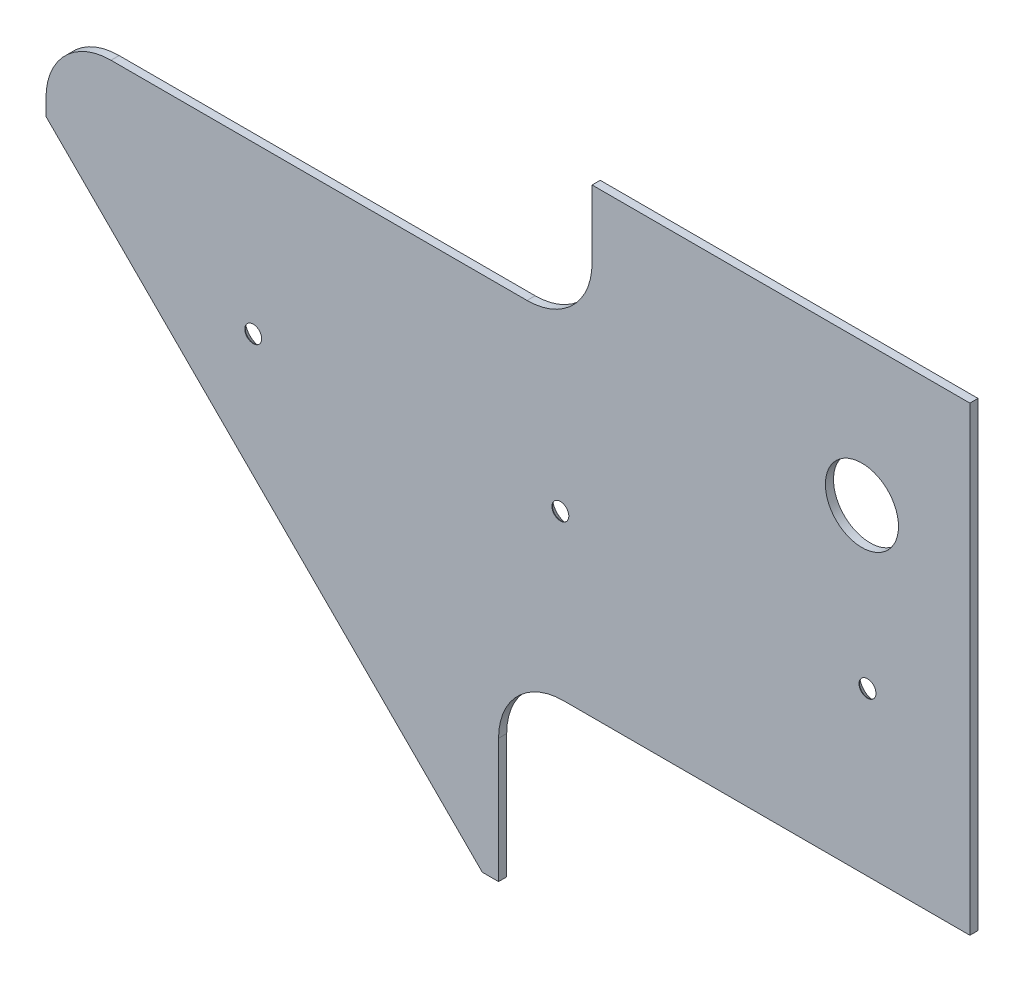
SolidWorks part; units mm, degrees
ref_plane "Front Plane" through (0, 0, 0) normal (0, 0, 1) x (1, 0, 0)
ref_plane "Top Plane" through (0, 0, 0) normal (0, 1, 0) x (1, 0, 0)
ref_plane "Right Plane" through (0, 0, 0) normal (1, 0, 0) x (0, 0, -1)
sketch "Sketch1" plane through (0, 0, 0) normal (0, 0, 1) x (1, 0, 0)
  line L0 (-138.2594, 48.9915) -> (32.2106, -121.4785)
  line L1 (32.2106, -121.4785) -> (222.7106, -121.4785)
  line L2 (-138.2594, 145.2215) -> (-138.2594, 48.9915)
  line L3 (-138.2594, 145.2215) -> (222.7106, 145.2215)
  line L4 (222.7106, -121.4785) -> (222.7106, 145.2215)
  circle A0 centre (180.538, 76.832) radius 14.2875
  circle A2 centre (180.538, 76.832) radius 64.9605 construction
  circle A3 centre (180.538, 76.832) radius 318.7974 construction
  point P0 (0, 0)
  point P2 (180.538, 76.832)
  dimension "D4" = 198.3105
  dimension "D1" = 45
  dimension "D2" = 266.7
  dimension "D5" = 245.11
extrude "Boss-Extrude1" add sketch "Sketch1" along normal blind 3.175
sketch "Sketch2" plane through (0, 0, 3.175) normal (0, 0, 1) x (1, 0, 0)
  line L0 (32.2106, -121.4785) -> (222.7106, -121.4785) construction
  line L1 (222.7634, -121.4785) -> (38.5606, -121.4785)
  line L2 (222.7634, -121.4785) -> (222.7634, -47.5645)
  line L3 (222.7634, -47.5645) -> (38.5606, -47.5645)
  line L4 (38.5606, -121.4785) -> (38.5606, -47.5645)
extrude "Cut-Extrude1" cut sketch "Sketch2" against normal through all contours L3 L4 L1 L2
fillet "Fillet1" radius 25.4 1 edges at (38.5606, -47.5645, 1.5875)
sketch "Sketch4" plane through (0, 0, 3.175) normal (0, 0, 1) x (1, 0, 0)
  line L1 (-138.2594, 145.2215) -> (-138.2594, 48.9915) construction
  line L3 (-138.2594, 145.2215) -> (75.1006, 145.2215)
  line L4 (-138.2594, 145.2215) -> (-138.2594, 80.7415)
  line L5 (-138.2594, 80.7415) -> (75.1006, 80.7415)
  line L6 (75.1006, 145.2215) -> (75.1006, 80.7415)
extrude "Cut-Extrude2" cut sketch "Sketch4" against normal through all contours L5 L6 L3 L4
fillet "Fillet2" radius 25.4 2 edges at (-138.2594, 80.7415, 1.5875) (75.1006, 80.7415, 1.5875)
sketch "Sketch7" plane through (0, 0, 3.175) normal (0, 0, 1) x (1, 0, 0)
  line L0 (222.7106, -47.5645) -> (222.7106, 145.2215) construction
  line L1 (75.1006, 145.2215) -> (222.7106, 145.2215)
  line L2 (75.1006, 145.2215) -> (75.1006, 132.5215)
  line L3 (75.1006, 132.5215) -> (222.7106, 132.5215)
  line L4 (222.7106, 145.2215) -> (222.7106, 132.5215)
  dimension "D1" = 12.7
extrude "Cut-Extrude4" cut sketch "Sketch7" against normal through all
hole_wizard "CSK for M6 Flat Head Machine Screw1" positions "Sketch9" profile "Sketch8" countersink size "M6" standard "ANSI Metric" end condition through all
sketch "Sketch9" plane through (0, 0, 0) normal (0, 0, -1) x (-1, 0, 0)
  line L1 (-222.7106, -47.5645) -> (-63.9606, -47.5645) construction
  line L5 (-222.7106, -47.5645) -> (-222.7106, 132.5215) construction
  point P0 (-182.7106, 15.9355)
  point P3 (-62.7106, 15.9355)
  point P6 (57.2894, 15.9355)
  dimension "D1" = 63.5
  dimension "D2" = 63.5
  dimension "D3" = 120
  dimension "D4" = 120
  dimension "D5" = 40
sketch "Sketch8" plane through (182.7106, 15.9355, 0) normal (1, 0, 0) x (0, 1, 0)
  line L0 (0, 0) -> (0, 3.175)
  line L1 (0, 3.175) -> (3.3, 3.175)
  line L2 (3.3, 3.175) -> (3.3, 3)
  line L3 (3.3, 3) -> (6.3, 0)
  line L5 (6.3, 0) -> (0, 0)
  line L6 (-3.3, 3) -> (-6.3, 0) construction
  line L11 (0, -6.35) -> (0, 107.95) construction
  dimension "Thru Hole Dia." = 6.6
  dimension "Thru Hole Depth" = 3.175
  dimension "Near C'Sink Dia." = 12.6
  dimension "Near C'Sink Angle" = 90
